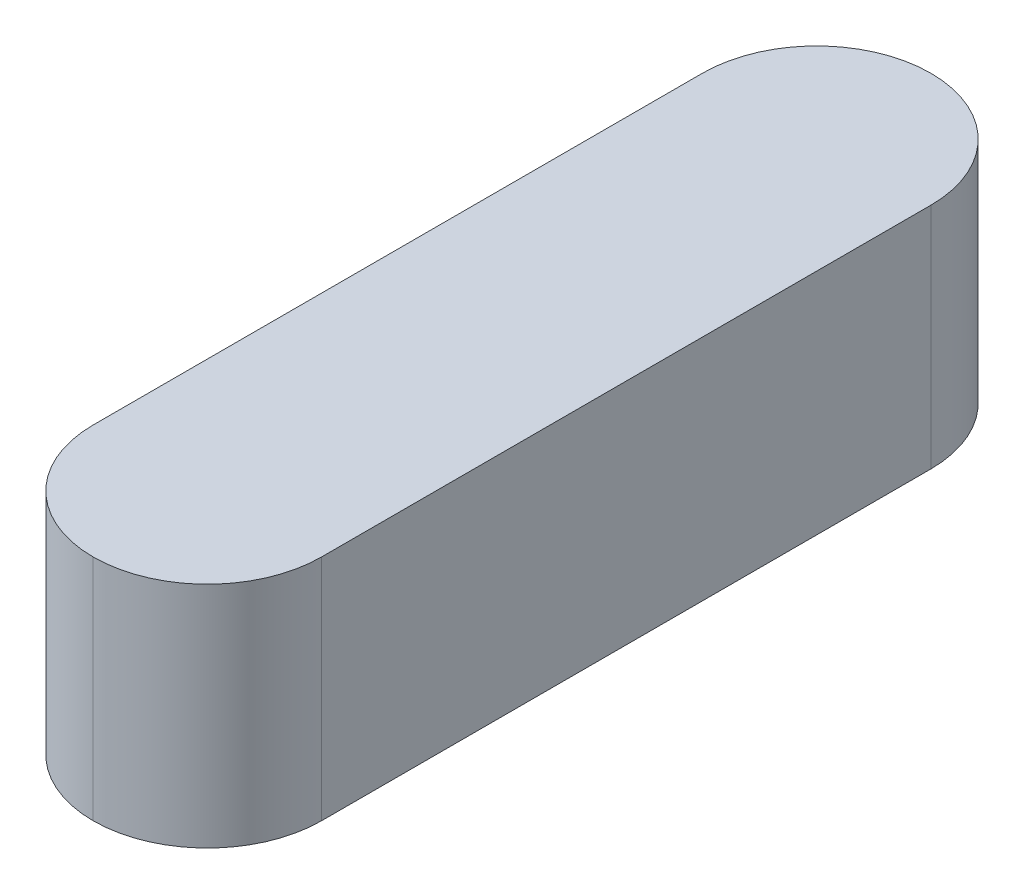
SolidWorks part; units mm, degrees
ref_plane "Front Plane" through (0, 0, 0) normal (0, 0, 1) x (1, 0, 0)
ref_plane "Top Plane" through (0, 0, 0) normal (0, 1, 0) x (1, 0, 0)
ref_plane "Right Plane" through (0, 0, 0) normal (1, 0, 0) x (0, 0, -1)
sketch "Sketch1" plane through (0, 0, 0) normal (0, 0, 1) x (1, 0, 0)
  line L1 (0, 1.9963) -> (6, 1.9963)
  line L2 (0, 1.9963) -> (0, 7.9963)
  line L3 (0, 7.9963) -> (6, 7.9963)
  line L4 (6, 1.9963) -> (6, 7.9963)
  dimension "D1" = 6
  dimension "D2" = 6
extrude "Extrude1" add sketch "Sketch1" along normal blind 22
fillet "Fillet1" radius 3 4 edges at (6, 4.9963, 22) (0, 4.9963, 22) (0, 4.9963, 0) (6, 4.9963, 0)
